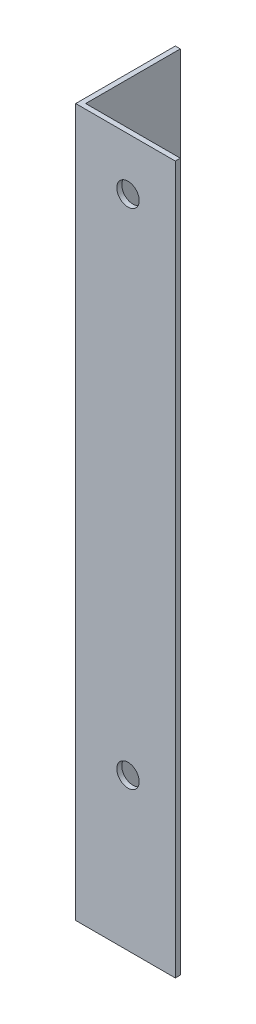
SolidWorks part; units mm, degrees
material "1060 Сплав"
ref_plane "Спереди" through (0, 0, 0) normal (0, 0, 1) x (1, 0, 0)
ref_plane "Сверху" through (0, 0, 0) normal (0, 1, 0) x (1, 0, 0)
ref_plane "Справа" through (0, 0, 0) normal (1, 0, 0) x (0, 0, -1)
sketch "Эскиз1" plane through (0, 0, 0) normal (0, 1, 0) x (1, 0, 0)
  line L0 (0, 0) -> (0, 20)
  line L1 (0, 20) -> (1, 20)
  line L2 (1, 20) -> (1, 1)
  line L3 (1, 1) -> (20, 1)
  line L4 (20, 1) -> (20, 0)
  line L5 (20, 0) -> (0, 0)
  dimension "D1" = 1
  dimension "D2" = 20
extrude "Бобышка-Вытянуть1" add sketch "Эскиз1" along normal blind 142
sketch "Эскиз2" plane through (0, 0, -1) normal (0, 0, -1) x (-1, 0, 0)
  line L0 (-10.5, 0) -> (-10.5, 142) construction
  line L1 (-20, 0) -> (-1, 0) construction
  line L2 (-20, 142) -> (-1, 142) construction
  circle A0 centre (-10.5, 131.5) radius 2.25
  dimension "D1" = 4.5
  dimension "D3" = 10.5
extrude "Вырез-Вытянуть1" cut sketch "Эскиз2" against normal through all
sketch "Эскиз3" plane through (0, 0, 0) normal (0, 0, 1) x (1, 0, 0)
  circle A0 centre (10.5, 30.5) radius 2.25 construction
  circle A1 centre (10.5, 30.5) radius 2.25
extrude "Вырез-Вытянуть2" cut sketch "Эскиз3" against normal through all
